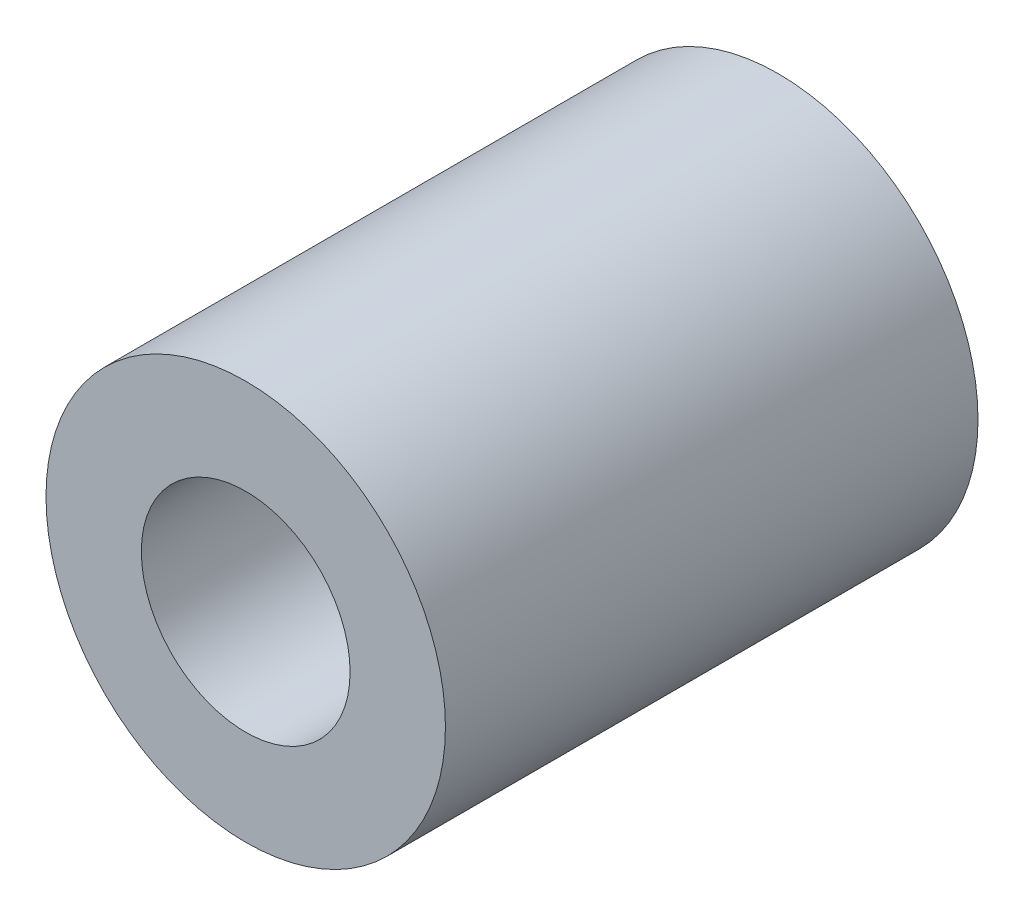
SolidWorks part; units mm, degrees
material "6061-T6 (SS)"
ref_plane "Front Plane" through (0, 0, 0) normal (0, 0, 1) x (1, 0, 0)
ref_plane "Top Plane" through (0, 0, 0) normal (0, 1, 0) x (1, 0, 0)
ref_plane "Right Plane" through (0, 0, 0) normal (1, 0, 0) x (0, 0, -1)
sketch "Sketch1" plane through (0, 0, 0) normal (0, 0, 1) x (1, 0, 0)
  circle A0 centre (0, 0) radius 2.4892
  circle A1 centre (0, 0) radius 4.7625
  dimension "D1" = 4.9784
  dimension "D2" = 9.525
extrude "Boss-Extrude1" add sketch "Sketch1" along normal blind 12.7
